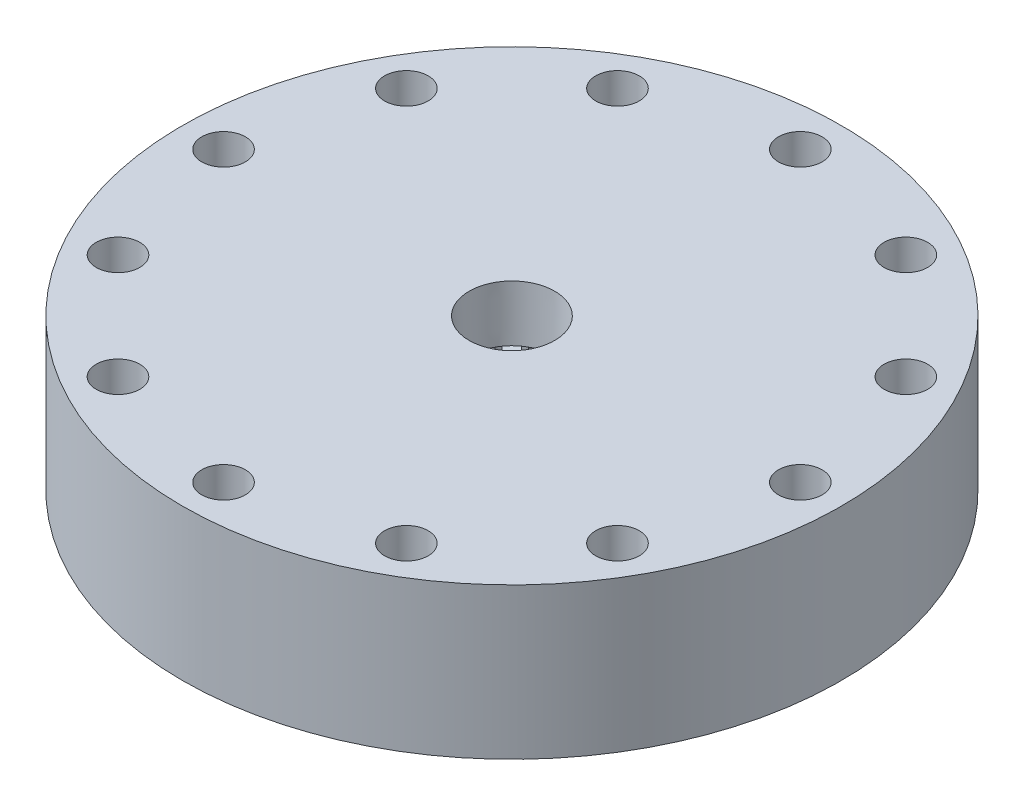
SolidWorks part; units mm, degrees
ref_plane "Front Plane" through (0, 0, 0) normal (0, 0, 1) x (1, 0, 0)
ref_plane "Top Plane" through (0, 0, 0) normal (0, 1, 0) x (1, 0, 0)
ref_plane "Right Plane" through (0, 0, 0) normal (1, 0, 0) x (0, 0, -1)
ref_axis "Axis1" through (0, 74.05, 0) along (0, -1, 0)
sketch "Sketch1" plane through (0, 0, 0) normal (0, 0, 1) x (1, 0, 0)
  line L2 (-76.2, 38.1) -> (0, 38.1)
  line L3 (0, 38.1) -> (0, 0)
  line L4 (0, 0) -> (-46.0375, 0)
  line L5 (-76.2, 38.1) -> (-76.2, 3.175)
  line L6 (-76.2, 3.175) -> (-55.5625, 3.175)
  line L8 (-55.5625, 3.175) -> (-52.3875, 3.175)
  line L9 (-52.3875, 3.175) -> (-46.0375, 9.525)
  line L10 (-46.0375, 0) -> (-46.0375, 9.525)
  dimension "D1" = 76.2
  dimension "D2" = 46.0375
  dimension "D4" = 3.175
  dimension "D5" = 135
  dimension "D6" = 3.175
  dimension "D7" = 6.35
  dimension "D8" = 38.1
revolve "Revolve1" add sketch "Sketch1" angle 360 about L3
ref_plane "Plane1" through (-46.0375, 0, 0) normal (-1, 0, 0) x (0, 0, 1)
sketch "Sketch6" plane through (-46.0375, 0, 0) normal (-1, 0, 0) x (0, 0, 1)
  line L0 (-3.175, 9.525) -> (3.175, 9.525)
  line L1 (3.175, 6.35) -> (0, 3.175)
  line L2 (0, 74.05) -> (0, -35.95) construction
  line L3 (0, 3.175) -> (-3.175, 6.35)
  line L4 (-3.175, 6.35) -> (3.175, 6.35) construction
  line L5 (-3.175, 6.35) -> (-3.175, 9.525)
  line L6 (3.175, 9.525) -> (3.175, 6.35)
  point P2 (0, 9.525)
  point P6 (0, 6.35)
  dimension "D1" = 90
  dimension "D2" = 3.175
  dimension "D3" = 6.35
  dimension "D4" = 6.35
extrude "Cut-Extrude1" cut sketch "Sketch6" against normal blind 20.6375
sketch "Sketch8" plane through (-46.0375, 0, 0) normal (-1, 0, 0) x (0, 0, 1)
  line L0 (0, 3.175) -> (-1.5875, 4.7625)
  line L1 (0, 74.05) -> (0, -35.95) construction
  line L2 (-1.5875, 4.7625) -> (-1.5875, 6.35)
  line L3 (0, 3.175) -> (1.5875, 4.7625)
  line L4 (1.5875, 4.7625) -> (1.5875, 6.35)
  line L5 (-1.5875, 4.7625) -> (1.5875, 4.7625) construction
  arc A0 (-1.5875, 6.35) -> (1.5875, 6.35) centre (0, 6.35) cw
  point P8 (0, 4.7625)
  point P10 (0, 7.9375)
  dimension "D1" = 90
  dimension "D2" = 3.175
  dimension "D3" = 4.7625
  dimension "D4" = 3.175
sketch "Sketch7" plane through (0, 0, 0) normal (0, 0, 1) x (1, 0, 0)
  line L1 (26.9875, 7.9375) -> (26.9875, 4.7625)
  line L2 (26.9875, 4.7625) -> (25.4, 3.175)
  line L3 (25.4, 3.175) -> (23.8125, 4.7625)
  line L4 (23.8125, 4.7625) -> (23.8125, 7.9375)
  line L5 (25.4, 3.175) -> (25.4, 7.9375) construction
  line L6 (26.9875, 4.7625) -> (23.8125, 4.7625) construction
  line L7 (0, 74.05) -> (0, -35.95) construction
  line L8 (23.8125, 7.9375) -> (26.9875, 7.9375) construction
  arc A0 (23.8125, 7.9375) -> (26.9875, 7.9375) centre (25.4, 7.9375) cw
  point P8 (25.4, 9.525)
  dimension "D1" = 3.175
  dimension "D2" = 6.35
  dimension "D3" = 25.4
  dimension "D4" = 3.175
revolve "Cut-Revolve1" cut sketch "Sketch7" angle 360 about axis through (0, 74.05, 0) along (0, -1, 0)
hole_wizard "3/64 (0.04688) Diameter Hole1" positions "Sketch10" profile "Sketch11" hole size "3/64" standard "ANSI Inch"
sketch "Sketch10" plane through (0, 0, 0) normal (0, -1, 0) x (-1, 0, 0)
  line L0 (0, 0) -> (38.9157, 0) construction
  line L2 (0, 0) -> (24.9119, 4.9553) construction
  point P0 (24.9119, 4.9553)
  dimension "D1" = 25.4
  dimension "D2" = 11.25
sketch "Sketch11" plane through (-24.9119, 0, -4.9553) normal (1, 0, 0) x (0, 0, -1)
  line L0 (0, 0) -> (0, 6.7077)
  line L1 (0, 6.7077) -> (0.5954, 6.35)
  line L2 (0.5954, 6.35) -> (0.5954, 0)
  line L5 (0.5954, 0) -> (0, 0)
  line L10 (0, 6.7077) -> (-0.5954, 6.35) construction
  line L11 (0, -6.35) -> (0, 107.95) construction
  dimension "Hole Dia." = 1.1908
  dimension "Hole Depth" = 6.35
  dimension "Drill Angle" = 118
hole_wizard "1/32 (0.03125) Diameter Hole1" positions "Sketch26" profile "Sketch27" hole size "1/32" standard "ANSI Inch"
sketch "Sketch26" plane through (0, 0, 0) normal (0, -1, 0) x (-1, 0, 0)
  line L3 (0, 0) -> (44.45, 0) construction
  point P0 (44.45, 0)
  point P22 (41.272, 0)
  dimension "D1" = 44.45
sketch "Sketch27" plane through (-44.45, 0, 0) normal (1, 0, 0) x (0, 0, -1)
  line L0 (0, 0) -> (0, 6.5885)
  line L1 (0, 6.5885) -> (0.3969, 6.35)
  line L2 (0.3969, 6.35) -> (0.3969, 0)
  line L5 (0.3969, 0) -> (0, 0)
  line L10 (0, 6.5885) -> (-0.3969, 6.35) construction
  line L11 (0, -6.35) -> (0, 107.95) construction
  dimension "Hole Dia." = 0.7937
  dimension "Hole Depth" = 6.35
  dimension "Drill Angle" = 118
sketch "Sketch12" plane through (0, 0, 0) normal (0, 0, 1) x (1, 0, 0)
  line L0 (0, 7.9375) -> (-11.1125, 19.05)
  line L1 (0, 74.05) -> (0, -35.95) construction
  line L2 (-11.1125, 19.05) -> (-11.1125, 25.4)
  line L6 (-11.1125, 25.4) -> (0, 25.4)
  line L7 (0, 25.4) -> (0, 7.9375)
  line L8 (-14.2875, 25.4) -> (-20.6375, 25.4)
  line L9 (-20.6375, 25.4) -> (-20.6375, 19.05)
  line L10 (-20.6375, 19.05) -> (-17.4625, 15.875)
  line L11 (-17.4625, 15.875) -> (-14.2875, 19.05)
  line L12 (-14.2875, 19.05) -> (-14.2875, 25.4)
  line L13 (-20.6375, 19.05) -> (-14.2875, 19.05) construction
  line L14 (76.2, 38.1) -> (-76.2, 38.1) construction
  line L15 (-30.1625, 25.4) -> (-34.925, 25.4)
  line L16 (-34.925, 25.4) -> (-34.925, 19.05)
  line L17 (-34.925, 19.05) -> (-32.5437, 16.6687)
  line L18 (-32.5437, 16.6687) -> (-30.1625, 19.05)
  line L19 (-30.1625, 19.05) -> (-30.1625, 25.4)
  line L20 (-34.925, 19.05) -> (-30.1625, 19.05) construction
  dimension "D1" = 45
  dimension "D2" = 135
  dimension "D3" = 3.175
  dimension "D4" = 6.35
  dimension "D5" = 11.1125
  dimension "D6" = 12.7
  dimension "D7" = 90
  dimension "D8" = 135
  dimension "D9" = 9.525
  dimension "D10" = 6.35
  dimension "D11" = 4.7625
  dimension "D12" = 6.35
  dimension "D13" = 6.35
revolve "Cut-Revolve2" cut sketch "Sketch12" angle 360 about axis through (0, 74.05, 0) along (0, -1, 0)
ref_plane "Plane2" through (-30.1625, 0, 0) normal (-1, 0, 0) x (0, 0, 1)
sketch "Sketch13" plane through (-30.1625, 0, 0) normal (-1, 0, 0) x (0, 0, 1)
  line L0 (1.5875, 25.4) -> (-1.5875, 25.4)
  line L1 (-1.5875, 25.4) -> (-1.5875, 22.225)
  line L2 (-1.5875, 22.225) -> (0, 20.6375)
  line L3 (0, 20.6375) -> (1.5875, 22.225)
  line L4 (1.5875, 22.225) -> (1.5875, 25.4)
  line L5 (-1.5875, 22.225) -> (1.5875, 22.225) construction
  line L6 (0, 74.05) -> (0, -35.95) construction
  line L7 (-30.1625, 25.4) -> (30.1625, 25.4) construction
  point P3 (0, 22.225)
  dimension "D1" = 3.175
  dimension "D2" = 4.7625
  dimension "D3" = 135
extrude "Cut-Extrude3" cut sketch "Sketch13" against normal up to surface (9.525 mm away) up to face at (0, 19.05, 20.6375)
ref_plane "Plane3" through (-14.2875, 0, 0) normal (-1, 0, 0) x (0, 0, 1)
sketch "Sketch14" plane through (-14.2875, 0, 0) normal (-1, 0, 0) x (0, 0, 1)
  line L0 (1.5875, 25.4) -> (-1.5875, 25.4)
  line L1 (-1.5875, 25.4) -> (-1.5875, 20.6375)
  line L2 (-1.5875, 20.6375) -> (0, 19.05)
  line L3 (0, 74.05) -> (0, -35.95) construction
  line L4 (0, 19.05) -> (1.5875, 20.6375)
  line L5 (1.5875, 20.6375) -> (1.5875, 25.4)
  line L6 (1.5875, 20.6375) -> (-1.5875, 20.6375) construction
  line L7 (-14.2875, 25.4) -> (14.2875, 25.4) construction
  point P2 (0, 20.6375)
  dimension "D1" = 135
  dimension "D2" = 6.35
  dimension "D3" = 3.175
extrude "Cut-Extrude4" cut sketch "Sketch14" against normal up to surface (3.175 mm away) up to face at (0, 19.05, 11.1125)
pattern_circular "CirPattern2" count 16 over 360 about axis through (0, 74.05, 0) along (0, -1, 0) of "Cut-Extrude3", "Cut-Extrude4"
ref_plane "Plane4" through (0, -4.7625, 0) normal (0, -1, 0) x (-1, 0, 0)
sketch "Sketch16" plane through (0, -4.7625, 0) normal (0, -1, 0) x (-1, 0, 0)
  line L0 (0, 0) -> (24.9119, 4.9553) construction
  line L1 (24.9119, 4.9553) -> (23.1363, 13.882) construction
  dimension "D1" = 90
ref_axis "Axis2" through (-24.9119, -4.7625, -4.9553) along (0.1951, 0, -0.9808)
ref_plane "Plane5" through (-10.1205, 10.3188, -2.0131) normal (0.6935, -0.7071, 0.1379) x (-0.1951, 0, 0.9808)
hole_wizard "3/64 (0.04688) Diameter Hole3" positions "Sketch17" profile "Sketch18" hole size "3/64" standard "ANSI Inch"
sketch "Sketch17" plane through (-10.1205, 10.3188, -2.0131) normal (0.6935, -0.7071, 0.1379) x (-0.1951, 0, 0.9808)
  point P0 (0, 21.3281)
sketch "Sketch18" plane through (-24.9119, -4.7625, -4.9553) normal (0.5437, 0.6393, 0.5437) x (0.4727, 0.3021, -0.8279)
  line L0 (0, 0) -> (0, 11.502)
  line L1 (0, 11.502) -> (0.5954, 11.1442)
  line L2 (0.5954, 11.1442) -> (0.5954, 0)
  line L5 (0.5954, 0) -> (0, 0)
  line L10 (0, 11.502) -> (-0.5954, 11.1442) construction
  line L11 (0, -6.35) -> (0, 107.95) construction
  dimension "Hole Dia." = 1.1908
  dimension "Hole Depth" = 11.1442
  dimension "Drill Angle" = 118
ref_plane "Plane6" through (-24.9119, 0, -4.9553) normal (-0.9808, 0, -0.1951) x (0.1951, 0, -0.9808)
ref_plane "Plane7" through (0, 19.05, 0) normal (0, -1, 0) x (-1, 0, 0)
hole_wizard "1/16 (0.0625) Diameter Hole1" positions "Sketch20" profile "Sketch21" hole size "1/16" standard "ANSI Inch"
sketch "Sketch20" plane through (0, 19.05, 0) normal (0, -1, 0) x (-1, 0, 0)
  line L1 (31.9184, 6.349) -> (0, 0) construction
  line L2 (0, 0) -> (22.3765, 0) construction
  circle A0 centre (0, 0) radius 32.5437 construction
  circle A1 centre (0, 0) radius 17.4625 construction
  point P0 (31.9184, 6.349)
  point P14 (17.127, 3.4068)
  dimension "D1" = 11.25
sketch "Sketch21" plane through (-31.9184, 19.05, -6.349) normal (1, 0, 0) x (0, 0, 1)
  line L0 (0, 0) -> (0, 16.4789)
  line L1 (0, 16.4789) -> (0.7937, 16.002)
  line L2 (0.7937, 16.002) -> (0.7937, 0)
  line L5 (0.7937, 0) -> (0, 0)
  line L10 (0, 16.4789) -> (-0.7938, 16.002) construction
  line L11 (0, -6.35) -> (0, 107.95) construction
  dimension "Hole Dia." = 1.5875
  dimension "Hole Depth" = 16.002
  dimension "Drill Angle" = 118
mirror "Mirror2" about plane through (-24.9119, 0, -4.9553) normal (-0.9808, 0, -0.1951) of "3/64 (0.04688) Diameter Hole3"
pattern_circular "CirPattern3" count 16 over 360 about axis through (0, 74.05, 0) along (0, -1, 0) of "3/64 (0.04688) Diameter Hole3", "Mirror2", "1/16 (0.0625) Diameter Hole1", "3/64 (0.04688) Diameter Hole1", "Cut-Extrude1", "1/32 (0.03125) Diameter Hole1"
hole_wizard "3/8 Clearance Hole1" positions "Sketch22" profile "Sketch23" hole size "3/8" standard "ANSI Inch" end condition through all
sketch "Sketch22" plane through (0, 38.1, 0) normal (0, 1, 0) x (1, 0, 0)
  line L0 (66.675, 0) -> (0, 0) construction
  point P0 (66.675, 0)
  dimension "D1" = 66.675
sketch "Sketch23" plane through (66.675, 38.1, 0) normal (1, 0, 0) x (0, 0, 1)
  line L0 (0, 0) -> (0, 38.1)
  line L1 (0, 38.1) -> (5.0419, 38.1)
  line L2 (5.0419, 38.1) -> (5.0419, 0)
  line L5 (5.0419, 0) -> (0, 0)
  line L11 (0, -6.35) -> (0, 107.95) construction
  dimension "Thru Hole Dia." = 10.0838
  dimension "Thru Hole Depth" = 38.1
pattern_circular "CirPattern4" count 12 over 360 about axis through (0, 74.05, 0) along (0, -1, 0) of "3/8 Clearance Hole1"
hole_wizard "1/2 NPT Tapped Hole2" positions "Sketch24" profile "Sketch25" size "1/2" standard "ANSI Inch"
sketch "Sketch24" plane through (0, 38.1, 0) normal (0, 1, 0) x (1, 0, 0)
  point P0 (0, 0)
cosmetic thread "Hole Thread2" parameters "D1"=13.462, "D2"=21.3288
sketch "Sketch25" plane through (0, 38.1, 0) normal (1, 0, 0) x (0, 0, 1)
  line L0 (0, 0) -> (0, 21.2395)
  line L1 (8.9281, 15.875) -> (0, 21.2395)
  line L2 (-8.9281, 15.875) -> (0, 21.2395) construction
  line L3 (8.9281, 15.875) -> (8.9281, 13.462)
  line L4 (8.9281, 13.462) -> (9.4797, 13.462)
  line L5 (9.4797, 13.462) -> (9.8828, 0)
  line L6 (-9.4797, 13.462) -> (-9.8828, 0) construction
  line L7 (9.8828, 0) -> (0, 0)
  line L8 (0, -6.35) -> (0, 107.95) construction
  line L11 (-8.9281, 13.462) -> (-9.4797, 13.462) construction
  dimension "Tap Drill Dia." = 17.8562
  dimension "Tap Drill Depth" = 15.875
  dimension "Thread Dia." = 19.7656
  dimension "Thread Angle" = 3.43
  dimension "Thread Depth" = 13.462
  dimension "Drill Angle" = 118
hole_wizard "1/2 NPT Tapped Hole1" positions "Sketch4" profile "Sketch5" size "1/2" standard "ANSI Inch"
sketch "Sketch4" plane through (0, 38.1, 0) normal (0, 1, 0) x (1, 0, 0)
  point P0 (0, 0)
sketch "Sketch5" plane through (0, 38.1, 0) normal (1, 0, 0) x (0, 0, 1)
  line L0 (0, 0) -> (0, 24.4145)
  line L1 (8.9281, 19.05) -> (0, 24.4145)
  line L2 (-8.9281, 19.05) -> (0, 24.4145) construction
  line L3 (8.9281, 19.05) -> (8.9281, 13.462)
  line L4 (8.9281, 13.462) -> (9.4797, 13.462)
  line L5 (9.4797, 13.462) -> (9.8828, 0)
  line L6 (-9.4797, 13.462) -> (-9.8828, 0) construction
  line L7 (9.8828, 0) -> (0, 0)
  line L8 (0, -6.35) -> (0, 107.95) construction
  line L11 (-8.9281, 13.462) -> (-9.4797, 13.462) construction
  dimension "Tap Drill Dia." = 17.8562
  dimension "Tap Drill Depth" = 19.05
  dimension "Thread Dia." = 19.7656
  dimension "Thread Angle" = 3.43
  dimension "Thread Depth" = 13.462
  dimension "Drill Angle" = 118
